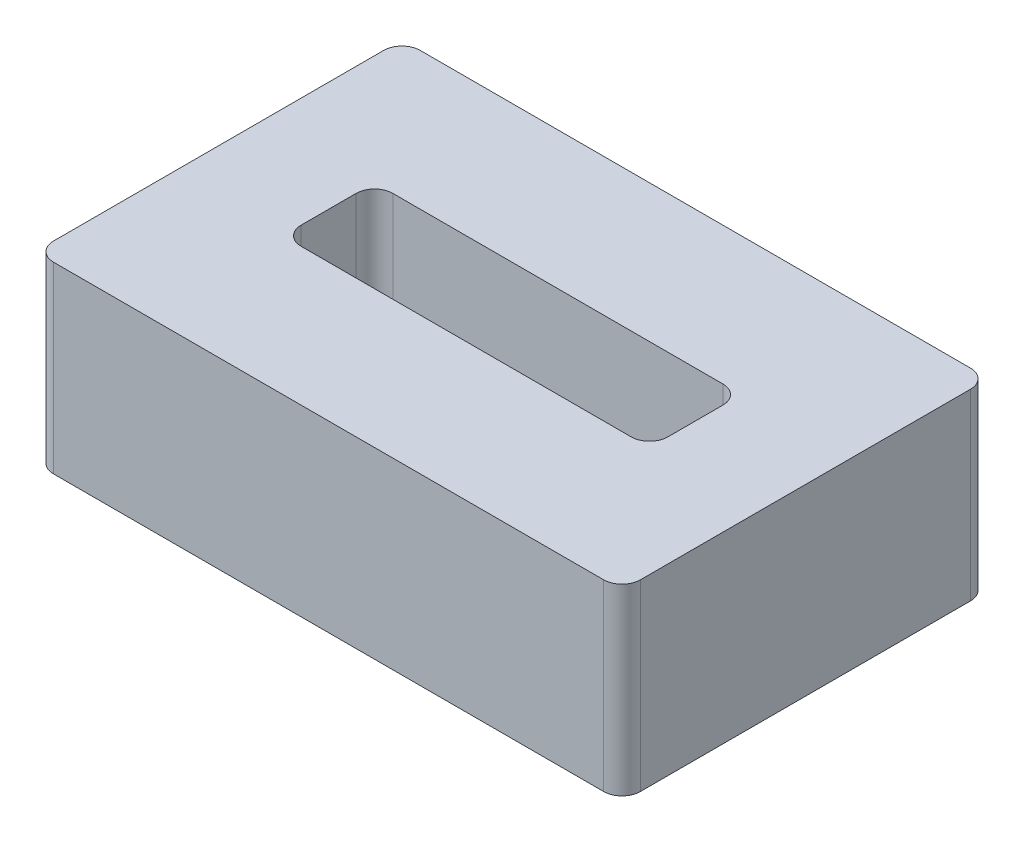
SolidWorks part; units mm, degrees
material "Rubber"
ref_plane "Front Plane" through (0, 0, 0) normal (0, 0, 1) x (1, 0, 0)
ref_plane "Top Plane" through (0, 0, 0) normal (0, 1, 0) x (1, 0, 0)
ref_plane "Right Plane" through (0, 0, 0) normal (1, 0, 0) x (0, 0, -1)
sketch "Sketch1" plane through (0, 0, 0) normal (0, 1, 0) x (1, 0, 0)
  line L1 (0, 0) -> (16, 0)
  line L2 (0, 0) -> (0, -10)
  line L3 (0, -10) -> (16, -10)
  line L4 (16, 0) -> (16, -10)
  line L5 (3, -3.75) -> (13, -3.75)
  line L10 (3, -3.75) -> (3, -6.25)
  line L11 (3, -6.25) -> (13, -6.25)
  line L12 (13, -3.75) -> (13, -6.25)
  dimension "D1" = 10
  dimension "D2" = 2.5
  dimension "D3" = 3.75
  dimension "D4" = 3
  dimension "D5" = 16
  dimension "D6" = 10
extrude "Boss-Extrude1" add sketch "Sketch1" along normal blind 5
fillet "Fillet3" radius 0.5 8 edges at (16, 2.5, 0) (16, 2.5, 10) (0, 2.5, 10) (0, 2.5, 0) (3, 2.5, 6.25) (13, 2.5, 6.25) (13, 2.5, 3.75) (3, 2.5, 3.75)
